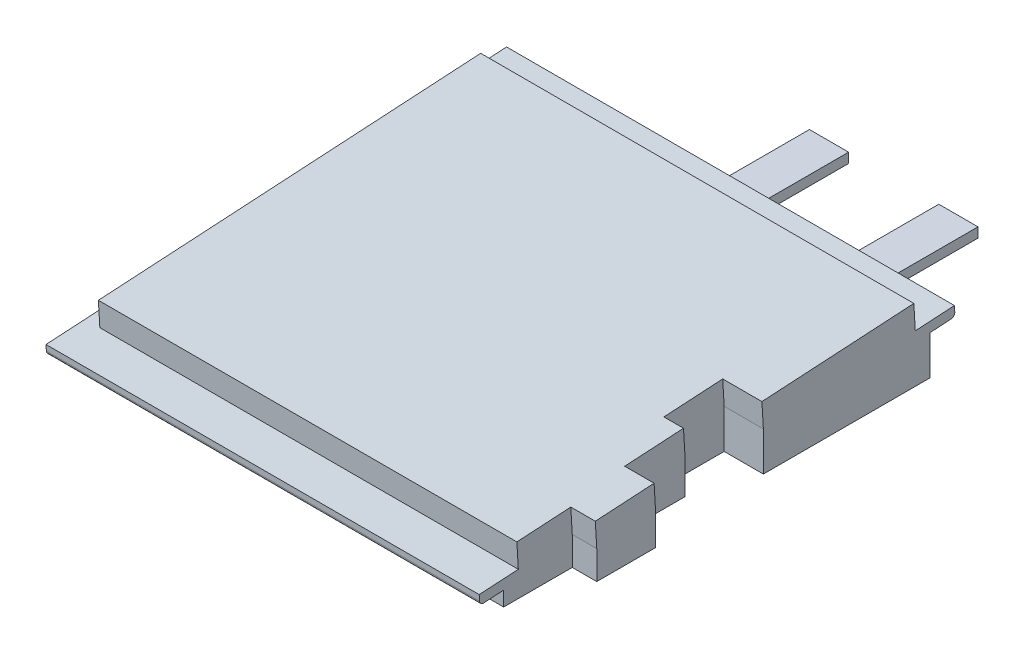
SolidWorks part; units mm, degrees
ref_plane "Front Plane" through (0, 0, 0) normal (0, 0, 1) x (1, 0, 0)
ref_plane "Top Plane" through (0, 0, 0) normal (0, 1, 0) x (1, 0, 0)
ref_plane "Right Plane" through (0, 0, 0) normal (1, 0, 0) x (0, 0, -1)
sketch "Sketch1" plane through (0, 0, 0) normal (0, 1, 0) x (1, 0, 0)
  line L0 (0, 0) -> (137.16, 0)
  line L1 (0, 0) -> (0, -133.35)
  line L2 (137.16, 0) -> (137.16, -53.975)
  line L3 (137.16, -53.975) -> (124.46, -53.975)
  line L4 (124.46, -53.975) -> (124.46, -73.025)
  line L5 (130.81, -73.025) -> (130.81, -92.075)
  line L6 (124.46, -73.025) -> (130.81, -73.025)
  line L7 (130.81, -92.075) -> (140.335, -92.075)
  line L8 (140.335, -92.075) -> (140.335, -111.125)
  line L9 (140.335, -111.125) -> (132.3975, -111.125)
  line L10 (132.3975, -111.125) -> (132.3975, -133.35)
  line L11 (0, -133.35) -> (132.3975, -133.35)
  dimension "D1" = 137.16
  dimension "D2" = 133.35
  dimension "D3" = 53.975
  dimension "D4" = 12.7
  dimension "D5" = 19.05
  dimension "D6" = 6.35
  dimension "D7" = 19.05
  dimension "D8" = 9.525
  dimension "D9" = 19.05
  dimension "D10" = 7.9375
extrude "Boss-Extrude1" add sketch "Sketch1" along normal blind 15.875
sketch "Sketch2" plane through (0, 0, 0) normal (-1, 0, 0) x (0, 0, 1)
  line L0 (133.35, 7.9375) -> (133.35, 15.875)
  line L1 (133.35, 15.875) -> (133.35, 0) construction
  line L2 (133.35, 15.875) -> (0, 15.875)
  line L3 (0, 15.875) -> (133.35, 7.9375)
  line L4 (0, 0) -> (133.35, 0) construction
  dimension "D1" = 7.9375
extrude "Cut-Extrude1" cut sketch "Sketch2" against normal through all
sketch "Sketch3" plane through (0, 15.819, 0.9416) normal (0, 0.9982, 0.0594) x (1, 0, 0)
  line L0 (0, 0.9433) -> (0, -132.6428) construction
  line L1 (-7.9375, 8.8808) -> (137.16, 8.8808)
  line L2 (-7.9375, 8.8808) -> (-7.9375, -140.5803)
  line L5 (137.16, 0.9433) -> (0, 0.9433) construction
  line L6 (-7.9375, -140.5803) -> (132.3975, -140.5803)
  line L7 (132.3975, -132.6428) -> (0, -132.6428) construction
  line L8 (132.3975, -110.3784) -> (132.3975, -132.6428) construction
  line L9 (132.3975, -140.5803) -> (132.3975, -124.7053)
  line L10 (132.3975, -124.7053) -> (7.9375, -124.7053)
  line L11 (7.9375, -124.7053) -> (7.9375, -6.9942)
  line L12 (7.9375, -6.9942) -> (137.16, -6.9942)
  line L13 (137.16, 0.9433) -> (137.16, -53.1273) construction
  line L14 (137.16, -6.9942) -> (137.16, 8.8808)
  dimension "D1" = 7.9375
  dimension "D2" = 7.9375
  dimension "D3" = 7.9375
  dimension "D4" = 0
  dimension "D5" = 7.9375
  dimension "D6" = 7.9375
  dimension "D7" = 7.9375
extrude "Boss-Extrude2" add sketch "Sketch3" against normal blind 3.175
fillet "Fillet1" radius 1.27 3 edges at (64.6113, 13.1772, -8.1121) (62.23, 4.2965, 141.0848) (-7.9375, 8.7369, 66.4863)
sketch "Sketch4" plane through (0, 15.819, 0.9416) normal (0, 0.9982, 0.0594) x (1, 0, 0)
  line L0 (-7.9375, 8.8808) -> (-7.9375, -140.5803) construction
  line L1 (-3.175, -3.8192) -> (103.8499, -3.8192)
  line L2 (-3.175, -3.8192) -> (-3.175, -127.8803)
  line L3 (-3.175, -127.8803) -> (132.3975, -127.8803)
  line L5 (-7.9375, -140.5803) -> (132.3975, -140.5803) construction
  line L6 (132.3975, -110.3784) -> (132.3975, -140.5803) construction
  line L7 (132.3975, -127.8803) -> (132.3975, -110.3784)
  line L8 (132.3975, -110.3784) -> (140.335, -110.3784)
  line L9 (140.335, -110.3784) -> (140.335, -91.2947)
  line L10 (140.335, -91.2947) -> (130.81, -91.2947)
  line L11 (130.81, -91.2947) -> (130.81, -72.211)
  line L12 (130.81, -72.211) -> (124.46, -72.211)
  line L13 (124.46, -72.211) -> (124.46, -53.1273)
  line L14 (124.46, -53.1273) -> (137.16, -53.1273)
  line L15 (137.16, -53.1273) -> (137.16, -3.8192)
  line L16 (137.16, 8.8808) -> (137.16, -53.1273) construction
  line L17 (137.16, -3.8192) -> (103.8499, -3.8192)
  line L18 (137.16, 8.8808) -> (-7.9375, 8.8808) construction
  dimension "D1" = 4.7625
  dimension "D2" = 12.7
  dimension "D3" = 0
  dimension "D4" = 12.7
  dimension "D5" = 17.5018
extrude "Boss-Extrude3" add sketch "Sketch4" along normal blind 7.9375
sketch "Sketch5" plane through (0, 0, 0) normal (0, 0, -1) x (-1, 0, 0)
  line L1 (-69.85, 9.2029) -> (-57.15, 9.2029)
  line L2 (-69.85, 9.2029) -> (-69.85, 6.0279)
  line L3 (-69.85, 6.0279) -> (-57.15, 6.0279)
  line L4 (-57.15, 9.2029) -> (-57.15, 6.0279)
  line L5 (-63.5, 6.0279) -> (-63.5, -5.0853) construction
  line L6 (0, 12.6944) -> (0, 0) construction
  line L7 (-105.41, 9.2029) -> (-105.41, -8.4766) construction
  line L8 (-111.76, 9.2029) -> (-99.06, 9.2029)
  line L9 (-111.76, 9.2029) -> (-111.76, 6.0279)
  line L10 (-111.76, 6.0279) -> (-99.06, 6.0279)
  line L11 (-99.06, 9.2029) -> (-99.06, 6.0279)
  line L12 (-137.16, 12.6944) -> (-137.16, 0) construction
  line L13 (-137.16, 16.3466) -> (7.9375, 16.3466) construction
  dimension "D1" = 63.5
  dimension "D2" = 31.75
  dimension "D3" = 12.7
  dimension "D4" = 3.175
  dimension "D5" = 3.175
  dimension "D6" = 12.7
  dimension "D7" = 7.1437
  dimension "D8" = 7.1437
extrude "Boss-Extrude4" add sketch "Sketch5" along normal blind 40.9575
